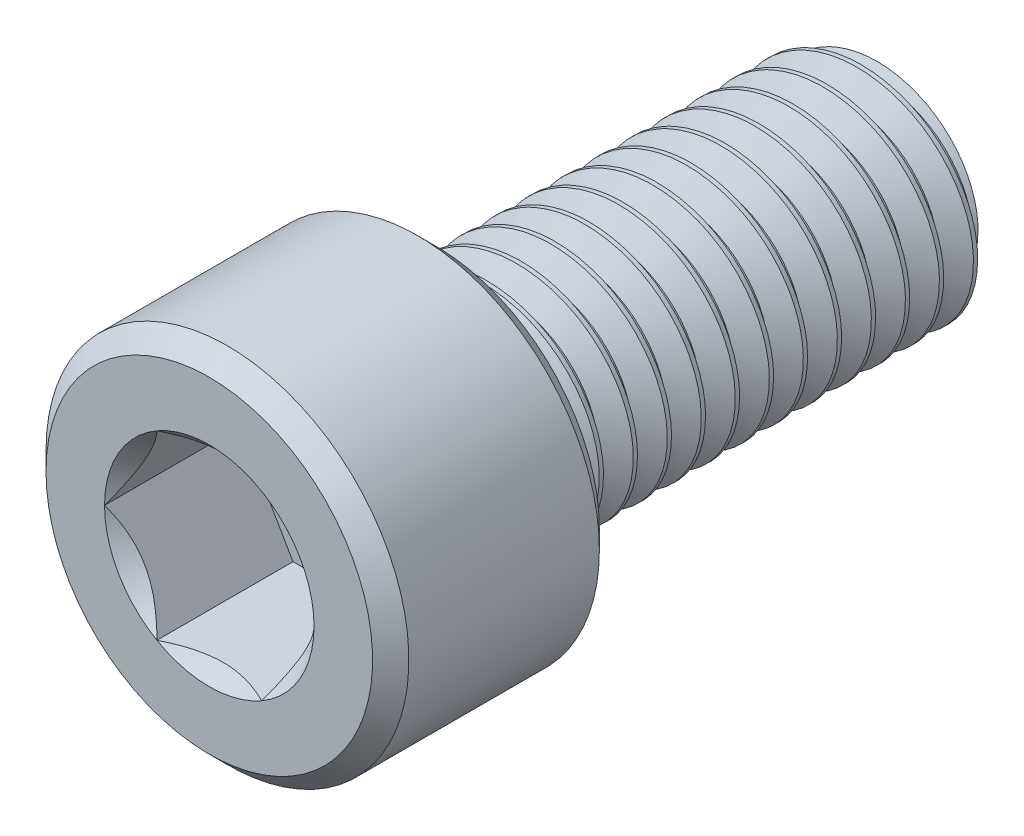
SolidWorks part; units mm, degrees
ref_plane "Front Plane" through (0, 0, 0) normal (0, 0, 1) x (1, 0, 0)
ref_plane "Top Plane" through (0, 0, 0) normal (0, 1, 0) x (1, 0, 0)
ref_plane "Right Plane" through (0, 0, 0) normal (1, 0, 0) x (0, 0, -1)
sketch "Sketch1" plane through (0, 0, 0) normal (0, 0, 1) x (1, 0, 0)
  circle A0 centre (0, 0) radius 5
  dimension "BODY DIAMETER" = 10
extrude "Boss-Extrude1" add sketch "Sketch1" along normal blind 20
sketch "Sketch2" plane through (0, 0, 0) normal (0, 0, -1) x (-1, 0, 0)
  circle A1 centre (0, 0) radius 5
  circle A2 centre (0, 0) radius 5
  dimension "D1" = 0
curve "Helix/Spiral1" pitch 1.5 height 45 turns 30 parameters "PITCH"=1.5
ref_plane "Plane1" through (0, 5, 0) normal (-0.9989, 0, 0.0477) x (0.0477, 0, 0.9989)
sketch "Sketch3" plane through (0, 5, 0) normal (-0.9989, 0, 0.0477) x (0.0477, 0, 0.9989)
  line L0 (0, 0) -> (-1.312, 0)
  line L1 (-1.312, 0) -> (-0.75, -0.9734)
  line L2 (-0.75, -0.9734) -> (-0.562, -0.9734)
  line L3 (-0.562, -0.9734) -> (0, 0)
  line L4 (-0.656, -0.9734) -> (-0.656, 0) construction
  line L5 (-1.031, -0.4867) -> (-0.281, -0.4867) construction
  dimension "D1" = 60
  dimension "THREAD DIM1" = 0.188
  dimension "THREAD DIM 2" = 0.75
sweep "Cut-Sweep1" cut profiles "Sketch3" path "Helix/Spiral1" align with end faces yes
sketch "Sketch4" plane through (0, 0, 0) normal (1, 0, 0) x (0, 0, -1)
  line L0 (0, 6) -> (-1.5597, 6)
  line L1 (-1.5597, 6) -> (0, 3.7726)
  line L2 (0, 3.7726) -> (0, 6)
  line L3 (0, 5) -> (1.3105, 5) construction
  line L4 (0, 0) -> (1.7976, 0) construction
  dimension "D1" = 55
  dimension "D2" = 1
  dimension "D3" = 0.254
revolve "Cut-Revolve1" cut sketch "Sketch4" angle 360 about L4
sketch "Sketch5" plane through (0, 0, 20) normal (0, 0, 1) x (1, 0, 0)
  circle A0 centre (0, 0) radius 8
  dimension "HEAD DIAMETER" = 16
extrude "Boss-Extrude2" add sketch "Sketch5" along normal blind 10
sketch "Sketch6" plane through (0, 0, 30) normal (0, 0, 1) x (1, 0, 0)
  line L1 (2.3094, 4) -> (-2.3094, 4)
  line L2 (-2.3094, 4) -> (-4.6188, 0)
  line L3 (-4.6188, 0) -> (-2.3094, -4)
  line L4 (-2.3094, -4) -> (2.3094, -4)
  line L5 (2.3094, -4) -> (4.6188, 0)
  line L6 (4.6188, 0) -> (2.3094, 4)
  circle A0 centre (0, 0) radius 4 construction
  dimension "HEX SOCKET SIZE" = 8
extrude "Cut-Extrude1" cut sketch "Sketch6" against normal blind 6
sketch "Sketch7" plane through (0, 0, 30) normal (0, 0, 1) x (1, 0, 0)
  circle A0 centre (0, 0) radius 4.6188
extrude "Cut-Extrude2" cut sketch "Sketch7" against normal through all draft 45
chamfer "Chamfer1" distance 0.8 angle 45 2 edges at (8, 0, 20) (8, 0, 30)
